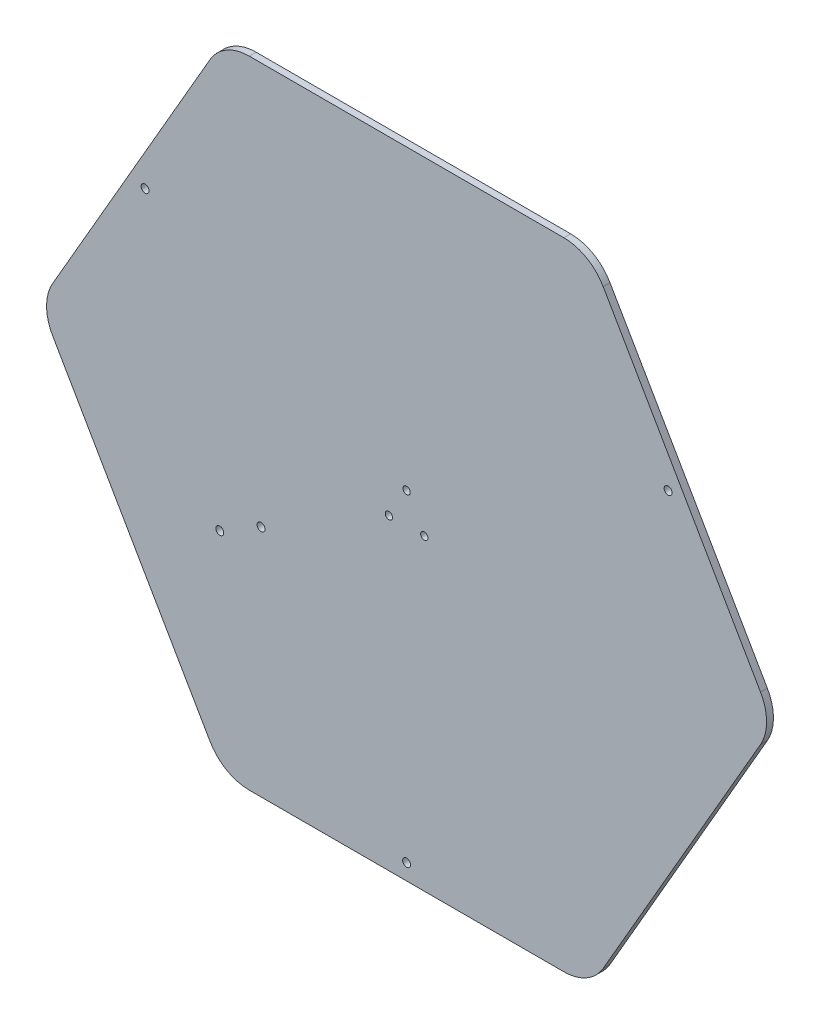
SolidWorks part; units mm, degrees
ref_plane "Alzado" through (0, 0, 0) normal (0, 0, 1) x (1, 0, 0)
ref_plane "Planta" through (0, 0, 0) normal (0, 1, 0) x (1, 0, 0)
ref_plane "Vista lateral" through (0, 0, 0) normal (1, 0, 0) x (0, 0, -1)
sketch "Croquis1" plane through (0, 0, 0) normal (0, 0, 1) x (1, 0, 0)
  line L0 (11.25, 96) -> (-11.25, 84) construction
  line L1 (-11.25, 96) -> (11.25, 96)
  line L2 (-11.25, 96) -> (-11.25, 84)
  line L3 (-11.25, 84) -> (11.25, 84)
  line L4 (11.25, 96) -> (11.25, 84)
  line L5 (-11.25, 96) -> (11.25, 84) construction
  line L6 (88.7634, -38.2572) -> (78.3711, -32.2572)
  line L7 (88.7634, -38.2572) -> (77.5134, -57.7428)
  line L8 (77.5134, -57.7428) -> (67.1211, -51.7428)
  line L9 (78.3711, -32.2572) -> (67.1211, -51.7428)
  line L10 (-77.5134, -57.7428) -> (-67.1211, -51.7428)
  line L11 (-77.5134, -57.7428) -> (-88.7634, -38.2572)
  line L12 (-88.7634, -38.2572) -> (-78.3711, -32.2572)
  line L13 (-67.1211, -51.7428) -> (-78.3711, -32.2572)
  line L14 (0, -0.7536) -> (0, 0) construction
  line L15 (0, 0) -> (0, 17.5) construction
  line L17 (-80.829, -140) -> (80.829, -140)
  line L18 (80.829, -140) -> (161.6581, 0)
  line L19 (161.6581, 0) -> (80.829, 140)
  line L20 (80.829, 140) -> (-80.829, 140)
  line L21 (-80.829, 140) -> (-161.6581, 0)
  line L22 (-161.6581, 0) -> (-80.829, -140)
  circle A0 centre (0, 0) radius 150
  circle A1 centre (0, 0) radius 10.8
  circle A2 centre (0, 0) radius 90 construction
  circle A3 centre (0, 90) radius 40 construction
  circle A4 centre (77.9423, -45) radius 40 construction
  circle A5 centre (-77.9423, -45) radius 40 construction
  circle A6 centre (0, 0) radius 17.5 construction
  circle A7 centre (0, 17.5) radius 2.6
  circle A8 centre (0, 0) radius 140 construction
  circle A9 centre (15.1554, -8.75) radius 2.6
  circle A10 centre (-15.1554, -8.75) radius 2.6
  point P11 (0, 90)
  point P18 (0, 0)
  point P28 (0, 0)
  point P39 (0, 0)
  dimension "D1" = 300
  dimension "D2" = 21.6
  dimension "D3" = 180
  dimension "D4" = 80
  dimension "D9" = 5.2
  dimension "D10" = 3
  dimension "D11" = 50
  dimension "D5" = 12
  dimension "D6" = 22.5
  dimension "D7" = 3
  dimension "D8" = 3
extrude "Saliente-Extruir1" add sketch "Croquis1" along normal blind 3 contours L19 A0 L20 L21 L22 L17 L18 A10 A9 A7 A1 L1 L4 L3 L2 L9 L6 L7 L8 L13 L10 L11 L12 | A0 L20 L21 | A0 L19 L20 | A0 L18 L19 | A0 L17 L18 | A0 L22 L17 | A0 L21 L22 | A10 | A1 | A9 | A7 | L11 L12 L13 L10 | L9 L8 L7 L6 | L3 L4 L1 L2 region at (-76.7492, -132.9335, 0) region at (-72.9482, -126.3499, 0) region at (76.7492, -132.9335, 0) region at (-153.4984, 0, 0) region at (153.4984, 0, 0) region at (-76.7492, 132.9335, 0) region at (76.7492, 132.9335, 0) region at (0, 0, 0) region at (0, 17.5, 0) region at (15.1554, -8.75, 0) region at (-15.1554, -8.75, 0)
fillet "Redondeo1" radius 20 6 edges at (80.829, 140, 1.5) (-80.829, 140, 1.5) (-161.6581, 0, 1.5) (-80.829, -140, 1.5) (80.829, -140, 1.5) (161.6581, 0, 1.5)
sketch "Croquis2" plane through (0, 0, 0) normal (0, 0, -1) x (1, 0, 0)
  circle A0 centre (0, 133) radius 1.75
  circle A1 centre (115.1814, -66.5) radius 1.75
  circle A2 centre (-115.1814, -66.5) radius 1.75
  point P9 (0, 0)
  dimension "D1" = 3
extrude "Cortar-Extruir1" cut sketch "Croquis2" against normal through all
sketch "Croquis3" plane through (0, 0, 86.15) normal (0, 0, 1) x (1, 0, 0)
  circle A0 centre (-64.0939, -37.0046) radius 1.75
  circle A1 centre (-82.2805, -47.5046) radius 1.75
  dimension "D1" = 3.5
extrude "Cortar-Extruir2" cut sketch "Croquis3" against normal through all
sketch "Croquis4" plane through (0, 0, 0) normal (0, 0, -1) x (1, 0, 0)
  circle A0 centre (7.7942, 4.5) radius 1.6
  circle A1 centre (0, -9) radius 1.6
  circle A2 centre (-7.7942, 4.5) radius 1.6
extrude "Cortar-Extruir3" cut sketch "Croquis4" against normal blind 3
